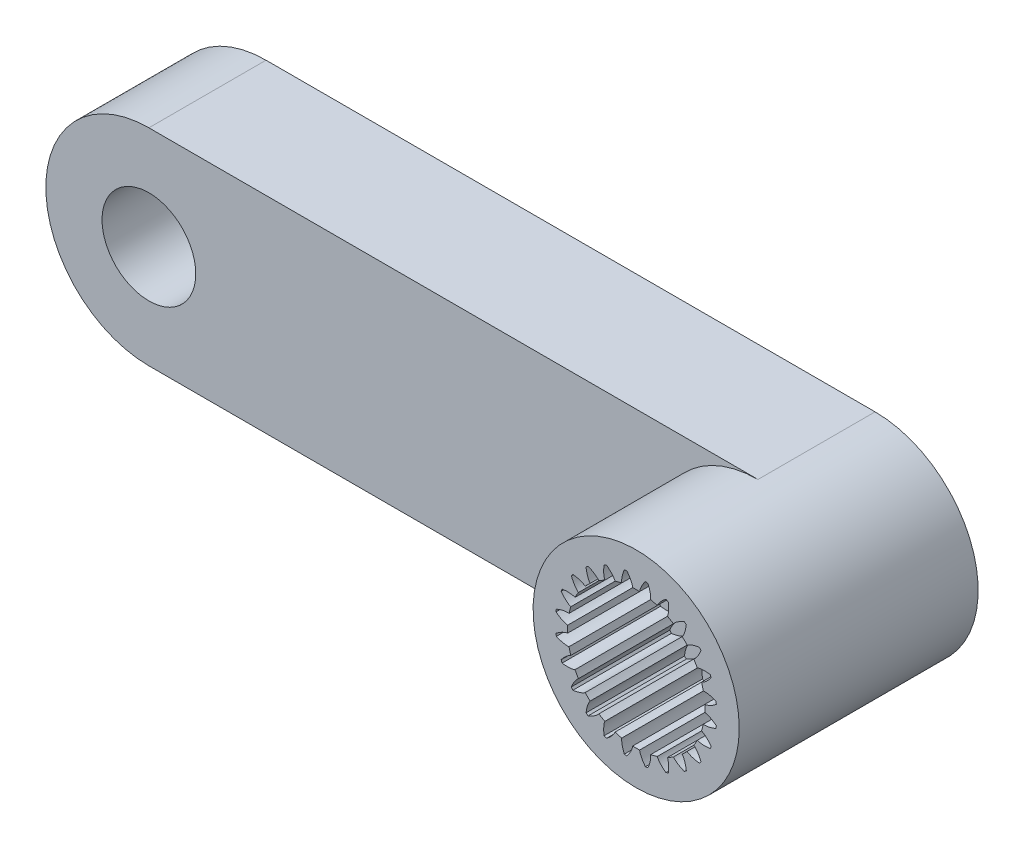
SolidWorks part; units mm, degrees
ref_plane "前视基准面" through (0, 0, 0) normal (0, 0, 1) x (1, 0, 0)
ref_plane "上视基准面" through (0, 0, 0) normal (0, 1, 0) x (1, 0, 0)
ref_plane "右视基准面" through (0, 0, 0) normal (1, 0, 0) x (0, 0, -1)
other "Configuration Table"
sketch "草图1" plane through (0, 0, 0) normal (0, 0, 1) x (1, 0, 0)
  circle A0 centre (0, 0) radius 1.7225
  circle A1 centre (0, 0) radius 1.9791
extrude "凸台-拉伸1" add sketch "草图1" along normal blind 2.1
ref_axis "基准轴1" through (0, 0, 2.1) along (0, 0, -1)
sketch "草图2" plane through (0, 0, 0) normal (0, 0, 1) x (1, 0, 0)
  line L0 (0, 0) -> (0, 1.4659) construction
  arc A0 (0.0741, 1.464) -> (-0.0741, 1.464) centre (0, 0) ccw
  arc A1 (0.2228, 1.7422) -> (-0.2228, 1.7422) centre (0, 0) ccw
  spline S0 degree 3 poles (0.0741, 1.464) (0.0743, 1.4676) (0.075, 1.4723) (0.0761, 1.4785) (0.077, 1.4828) (0.0781, 1.4876) (0.0794, 1.493) (0.081, 1.499) (0.0829, 1.5055) (0.0851, 1.5125) (0.0876, 1.52) (0.0904, 1.528) (0.0936, 1.5365) (0.0972, 1.5455) (0.1012, 1.5549) (0.1057, 1.5648) (0.1105, 1.5752) (0.1159, 1.5859) (0.1217, 1.5971) (0.1281, 1.6087) (0.1349, 1.6206) (0.1423, 1.633) (0.1503, 1.6456) (0.1588, 1.6586) (0.1679, 1.6719) (0.1776, 1.6855) (0.188, 1.6994) (0.2028, 1.7185) (0.2146, 1.7327) (0.2228, 1.7422) knots 0 0 0 0 0.033052 0.04499 0.058764 0.074375 0.091822 0.111106 0.132226 0.155183 0.179977 0.206607 0.235073 0.265377 0.297516 0.331493 0.367306 0.404955 0.444441 0.485764 0.528923 0.573918 0.620751 0.66942 0.719925 0.772267 0.826445 0.88246 1 1 1 1
  spline S1 degree 3 poles (-0.0741, 1.464) (-0.0743, 1.4676) (-0.075, 1.4723) (-0.0761, 1.4785) (-0.077, 1.4828) (-0.0781, 1.4876) (-0.0794, 1.493) (-0.081, 1.499) (-0.0829, 1.5055) (-0.0851, 1.5125) (-0.0876, 1.52) (-0.0904, 1.528) (-0.0936, 1.5365) (-0.0972, 1.5455) (-0.1012, 1.5549) (-0.1057, 1.5648) (-0.1105, 1.5752) (-0.1159, 1.5859) (-0.1217, 1.5971) (-0.1281, 1.6087) (-0.1349, 1.6206) (-0.1423, 1.633) (-0.1503, 1.6456) (-0.1588, 1.6586) (-0.1679, 1.6719) (-0.1776, 1.6855) (-0.188, 1.6994) (-0.2028, 1.7185) (-0.2146, 1.7327) (-0.2228, 1.7422) knots 0 0 0 0 0.033052 0.04499 0.058764 0.074375 0.091822 0.111106 0.132226 0.155183 0.179977 0.206607 0.235073 0.265377 0.297516 0.331493 0.367306 0.404955 0.444441 0.485764 0.528923 0.573918 0.620751 0.66942 0.719925 0.772267 0.826445 0.88246 1 1 1 1
extrude "凸台-拉伸2" add sketch "草图2" along normal blind 2.1
pattern_circular "阵列(圆周)1" count 24 every 15 about axis through (0, 0, 2.1) along (0, 0, -1) of "凸台-拉伸2"
sketch "草图3" plane through (0, 0, 0) normal (0, 0, -1) x (-1, 0, 0)
  circle A0 centre (0, 0) radius 1.9791 construction
  circle A1 centre (0, 0) radius 1.9791
  circle A2 centre (0, 0) radius 2.2
  dimension "D1" = 4.4
extrude "凸台-拉伸3" add sketch "草图3" against normal up to surface (2.1 mm away) up to face at (0, 0, 2.1)
sketch "草图4" plane through (0, 0, 0) normal (0, 0, -1) x (-1, 0, 0)
  circle A1 centre (0, 0) radius 2.2
  circle A2 centre (0, 0) radius 2.2
  dimension "D1" = 0
extrude "凸台-拉伸4" add sketch "草图4" along normal blind 3
sketch "草图7" plane through (0, 0, -3) normal (0, 0, -1) x (-1, 0, 0)
  line L0 (0, 2.2) -> (13, 2.2)
  line L1 (0, -2.2) -> (13, -2.2)
  circle A0 centre (0, 0) radius 2.2 construction
  arc A1 (13, 2.2) -> (13, -2.2) centre (13, 0) cw
  arc A2 (0, 2.2) -> (0, -2.2) centre (0, 0) ccw
  dimension "D1" = 13
  dimension "D2" = 13
extrude "凸台-拉伸5" add sketch "草图7" against normal blind 2.5
sketch "草图8" plane through (0, 0, 0) normal (0, 0, 1) x (1, 0, 0)
  circle A0 centre (0, 0) radius 1
  dimension "D1" = 2
extrude "切除-拉伸3" cut sketch "草图8" against normal blind 1
sketch "草图9" plane through (0, 0, -3) normal (0, 0, -1) x (-1, 0, 0)
  circle A0 centre (0, 0) radius 0.75
  dimension "D1" = 1.5
extrude "切除-拉伸4" cut sketch "草图9" against normal blind 2
sketch "草图10" plane through (0, 0, -0.5) normal (0, 0, 1) x (1, 0, 0)
  line L0 (-13, 0) -> (0, 0) construction
  circle A0 centre (-13, 0) radius 1
  dimension "D1" = 2
  dimension "D2" = 13
extrude "切除-拉伸5" cut sketch "草图10" against normal through all
sketch "草图11" plane through (0, 0, -0.5) normal (0, 0, 1) x (1, 0, 0)
  line L0 (0, 0) -> (-13, 0)
